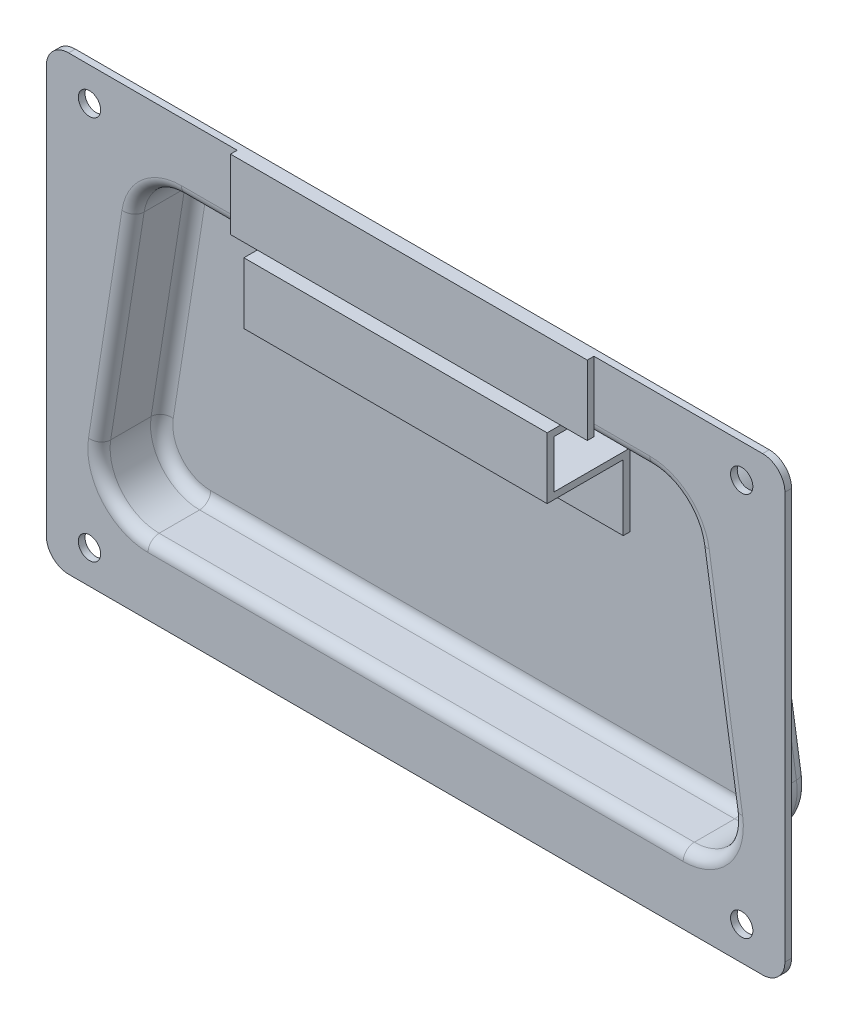
SolidWorks part; units mm, degrees
ref_plane "Front Plane" through (0, 0, 0) normal (0, 0, 1) x (1, 0, 0)
ref_plane "Top Plane" through (0, 0, 0) normal (0, 1, 0) x (1, 0, 0)
ref_plane "Right Plane" through (0, 0, 0) normal (1, 0, 0) x (0, 0, -1)
sketch "Sketch1" plane through (0, 0, 0) normal (0, 0, 1) x (1, 0, 0)
  line L1 (-66.25, -40.5) -> (66.25, -40.5)
  line L2 (-66.25, -40.5) -> (-66.25, 40.5)
  line L3 (-66.25, 40.5) -> (66.25, 40.5)
  line L4 (66.25, -40.5) -> (66.25, 40.5)
  line L5 (-66.25, -40.5) -> (66.25, 40.5) construction
  line L6 (-66.25, 40.5) -> (66.25, -40.5) construction
  point P0 (0, 0)
  dimension "D1" = 132.5
  dimension "D2" = 81
extrude "Boss-Extrude1" add sketch "Sketch1" against normal blind 1.2
sketch "Sketch2" plane through (0, 0, -1.2) normal (0, 0, -1) x (-1, 0, 0)
  line L0 (-42, 29.2) -> (42, 29.2)
  line L1 (51.8801, 20.7438) -> (57.8801, -17.6562)
  line L2 (48, -29.2) -> (-48, -29.2)
  line L3 (-57.8801, -17.6562) -> (-51.8801, 20.7438)
  line L4 (0, 29.2) -> (0, -29.2) construction
  line L5 (-48, -19.2) -> (-58, -19.2) construction
  line L6 (-58, -19.2) -> (58, -19.2) construction
  arc A0 (57.8801, -17.6562) -> (48, -29.2) centre (48, -19.2) cw
  arc A1 (-48, -29.2) -> (-57.8801, -17.6562) centre (-48, -19.2) cw
  arc A2 (42, 29.2) -> (51.8801, 20.7438) centre (42, 19.2) cw
  arc A3 (-42, 29.2) -> (-51.8801, 20.7438) centre (-42, 19.2) ccw
  point P6 (0, 0)
  dimension "D2" = 10
  dimension "D1" = 58.4
  dimension "D3" = 116
  dimension "D4" = 84
extrude "Extrude-Thin1" add sketch "Sketch2" along normal blind 11.25 thin thin type one direction reverse wall 1.2
sketch "Sketch3" plane through (0, 0, -1.2) normal (0, 0, -1) x (-1, 0, 0)
  line L4 (56.6945, -17.8415) -> (50.6945, 20.5585)
  line L5 (42, 28) -> (-42, 28)
  line L6 (-50.6945, 20.5585) -> (-56.6945, -17.8415)
  line L7 (-48, -28) -> (48, -28)
  line L8 (56.6945, -17.8415) -> (50.6945, 20.5585)
  line L9 (42, 28) -> (-42, 28)
  line L10 (-50.6945, 20.5585) -> (-56.6945, -17.8415)
  line L11 (-48, -28) -> (48, -28)
  arc A4 (48, -28) -> (56.6945, -17.8415) centre (48, -19.2) ccw
  arc A5 (50.6945, 20.5585) -> (42, 28) centre (42, 19.2) ccw
  arc A6 (-42, 28) -> (-50.6945, 20.5585) centre (-42, 19.2) ccw
  arc A7 (-56.6945, -17.8415) -> (-48, -28) centre (-48, -19.2) ccw
  arc A8 (48, -28) -> (56.6945, -17.8415) centre (48, -19.2) ccw
  arc A9 (50.6945, 20.5585) -> (42, 28) centre (42, 19.2) ccw
  arc A10 (-42, 28) -> (-50.6945, 20.5585) centre (-42, 19.2) ccw
  arc A11 (-56.6945, -17.8415) -> (-48, -28) centre (-48, -19.2) ccw
  dimension "D1" = 0
extrude "Cut-Extrude1" cut sketch "Sketch3" against normal through all
sketch "Sketch4" plane through (0, 0, -12.45) normal (0, 0, -1) x (-1, 0, 0)
  line L0 (-51.8801, 20.7438) -> (-57.8801, -17.6562) construction
  line L1 (-51.8801, 20.7438) -> (-57.8801, -17.6562)
  line L2 (42, 29.2) -> (-42, 29.2) construction
  line L3 (57.8801, -17.6562) -> (51.8801, 20.7438) construction
  line L4 (-48, -29.2) -> (48, -29.2) construction
  line L5 (42, 29.2) -> (-42, 29.2)
  line L6 (57.8801, -17.6562) -> (51.8801, 20.7438)
  line L7 (-48, -29.2) -> (48, -29.2)
  arc A0 (-42, 29.2) -> (-51.8801, 20.7438) centre (-42, 19.2) ccw construction
  arc A1 (51.8801, 20.7438) -> (42, 29.2) centre (42, 19.2) ccw construction
  arc A2 (48, -29.2) -> (57.8801, -17.6562) centre (48, -19.2) ccw construction
  arc A3 (-57.8801, -17.6562) -> (-48, -29.2) centre (-48, -19.2) ccw construction
  arc A4 (-42, 29.2) -> (-51.8801, 20.7438) centre (-42, 19.2) ccw
  arc A5 (51.8801, 20.7438) -> (42, 29.2) centre (42, 19.2) ccw
  arc A6 (48, -29.2) -> (57.8801, -17.6562) centre (48, -19.2) ccw
  arc A7 (-57.8801, -17.6562) -> (-48, -29.2) centre (-48, -19.2) ccw
extrude "Boss-Extrude2" add sketch "Sketch4" against normal blind 1.2
fillet "Fillet1" radius 2 32 edges at (-48.5024, 26.7973, -12.45) (-54.8801, 1.5438, -12.45) (-55.5973, -25.7024, -12.45) (0, -29.2, -12.45) (55.5973, -25.7024, -12.45) (54.8801, 1.5438, -12.45) (48.5024, 26.7973, -12.45) (-47.7221, 25.8856, 0) (-53.6945, 1.3585, 0) (-54.6856, -24.9221, 0) (0, -28, 0) (54.6856, -24.9221, 0) (53.6945, 1.3585, 0) (47.7221, 25.8856, 0) (0, 29.2, -12.45) (0, 28, 0) (-47.7221, 25.8856, -11.25) (-53.6945, 1.3585, -11.25) (-54.6856, -24.9221, -11.25) (0, -28, -11.25) (54.6856, -24.9221, -11.25) (53.6945, 1.3585, -11.25) (47.7221, 25.8856, -11.25) (48.5024, 26.7973, -1.2) (0, 29.2, -1.2) (-48.5024, 26.7973, -1.2) (-54.8801, 1.5438, -1.2) (-55.5973, -25.7024, -1.2) (0, -29.2, -1.2) (55.5973, -25.7024, -1.2) (0, 28, -11.25) (54.8801, 1.5438, -1.2)
fillet "Fillet2" radius 4 4 edges at (-66.25, -40.5, -0.6) (-66.25, 40.5, -0.6) (66.25, 40.5, -0.6) (66.25, -40.5, -0.6)
hole_wizard "Ø4.0 (4) Diameter Hole1" positions "Sketch6" profile "Sketch5" hole size "Ø4.0" standard "ANSI Metric" end condition through all
sketch "Sketch6" plane through (0, 0, 0) normal (0, 0, 1) x (1, 0, 0)
  line L1 (58.5, -34.5) -> (-58.5, -34.5) construction
  line L2 (58.5, -34.5) -> (58.5, 34.5) construction
  line L3 (58.5, 34.5) -> (-58.5, 34.5) construction
  line L4 (-58.5, -34.5) -> (-58.5, 34.5) construction
  line L5 (58.5, -34.5) -> (-58.5, 34.5) construction
  line L6 (58.5, 34.5) -> (-58.5, -34.5) construction
  point P0 (-58.5, 34.5)
  point P2 (58.5, 34.5)
  point P4 (58.5, -34.5)
  point P6 (-58.5, -34.5)
  point P85 (0, 0)
  dimension "D1" = 69
  dimension "D2" = 117
sketch "Sketch5" plane through (-58.5, 34.5, 0) normal (1, 0, 0) x (0, -1, 0)
  line L0 (0, 0) -> (0, 12.45)
  line L1 (0, 12.45) -> (2, 12.45)
  line L2 (2, 12.45) -> (2, 0)
  line L5 (2, 0) -> (0, 0)
  line L11 (0, -6.35) -> (0, 107.95) construction
  dimension "Thru Hole Dia." = 4
  dimension "Thru Hole Depth" = 12.45
sketch "Sketch7" plane through (0, 0, 0) normal (1, 0, 0) x (0, 0, -1)
  line L0 (0, 40.5) -> (0, 26.8)
  line L1 (0, 30) -> (0, 20.8673) construction
  line L2 (0, 26.8) -> (-2.4, 26.8)
  line L3 (-2.4, 26.8) -> (-2.4, 18.2)
  line L4 (-2.4, 18.2) -> (11.25, 18.2)
  line L5 (11.25, -18.1502) -> (11.25, 20.2498) construction
  line L6 (11.25, 18.2) -> (11.25, 5.2)
  line L7 (11.25, 5.2) -> (10.05, 5.2)
  line L8 (10.05, 5.2) -> (10.05, 17)
  line L9 (10.05, 17) -> (-3.6, 17)
  line L10 (-3.6, 17) -> (-3.6, 28)
  line L11 (-3.6, 28) -> (-1.2, 28)
  line L12 (-1.2, 28) -> (-1.2, 40.5)
  line L13 (-1.2, 40.5) -> (0, 40.5)
  line L14 (8.8901, 28) -> (-0.4532, 28) construction
  line L15 (9.25, 28) -> (2, 28) construction
  dimension "D1" = 1.2
  dimension "D2" = 1.2
  dimension "D3" = 1.2
  dimension "D4" = 1.2
  dimension "D5" = 1.2
  dimension "D6" = 2.4
  dimension "D7" = 13
  dimension "D8" = 11
extrude "Boss-Extrude3" add sketch "Sketch7" along normal mid plane 64
sketch "Sketch9" plane through (-32, 0, 0) normal (-1, 0, 0) x (0, 0, 1)
  line L0 (2.4, 18.2) -> (2.4, 26.8) construction
  line L1 (3.6, 28) -> (3.6, 17) construction
  line L2 (3.6, 17) -> (-10.05, 17) construction
  line L3 (-11.25, 18.2) -> (2.4, 18.2) construction
  line L4 (-11.25, 5.2) -> (-11.25, 18.2) construction
  line L5 (-10.05, 17) -> (-10.05, 5.2) construction
  line L6 (-10.05, 5.2) -> (-11.25, 5.2) construction
  line L7 (2.4, 18.2) -> (2.4, 26.8)
  line L8 (3.6, 28) -> (3.6, 17)
  line L9 (3.6, 17) -> (-10.05, 17)
  line L10 (-11.25, 18.2) -> (2.4, 18.2)
  line L11 (-11.25, 5.2) -> (-11.25, 18.2)
  line L12 (-10.05, 17) -> (-10.05, 5.2)
  line L13 (-10.05, 5.2) -> (-11.25, 5.2)
  line L14 (3.6, 28) -> (0, 28)
  line L15 (0, 26.8) -> (0, 30) construction
  line L16 (0, 28) -> (0, 26.8)
  line L17 (2.4, 26.8) -> (0, 26.8) construction
  line L18 (0, 26.8) -> (2.4, 26.8)
extrude "Cut-Extrude3" cut sketch "Sketch9" against normal blind 4.8
mirror "Mirror1" about plane through (0, 0, 0) normal (1, 0, 0) of "Cut-Extrude3"
sketch "Sketch10" plane through (0, 0, -1.2) normal (0, 0, -1) x (-1, 0, 0)
  line L0 (-60, -19.2) -> (-60, -36.1742) construction
  line L1 (60, -19.2) -> (60, -36.6486) construction
  arc A0 (-59.8561, -17.3475) -> (-48, -31.2) centre (-48, -19.2) ccw construction
  arc A1 (48, -31.2) -> (59.8561, -17.3475) centre (48, -19.2) ccw construction
sketch "Sketch12" plane through (0, 0, 0) normal (1, 0, 0) x (0, 0, -1)
  line L0 (12.45, 9.5) -> (17.9127, 9.5) construction
  line L1 (12.45, 20.435) -> (12.45, -17.965) construction
  line L2 (12.45, 12.65) -> (12.7483, 12.4321)
  line L3 (12.7483, 11.2439) -> (12.45, 11.0262)
  line L4 (12.45, 11.0262) -> (12.45, 12.65)
  line L5 (12.45, 11.8381) -> (13.05, 11.838) construction
  line L6 (0, 40.5) -> (1.2, 40.5) construction
  arc A0 (12.7483, 12.4321) -> (12.7483, 11.2439) centre (12.3143, 11.838) cw
  dimension "D1" = 3.15
  dimension "D2" = 31
  dimension "D3" = 0.6
  dimension "D4" = 1.6238
revolve "Revolve1" add sketch "Sketch12" angle 360 about L0
pattern_linear "LPattern1" count 2 spacing 25.5 along (-1, 0, 0) count 2 spacing 25.5 along (1, 0, 0) skipping (1, 1) of "Revolve1"
